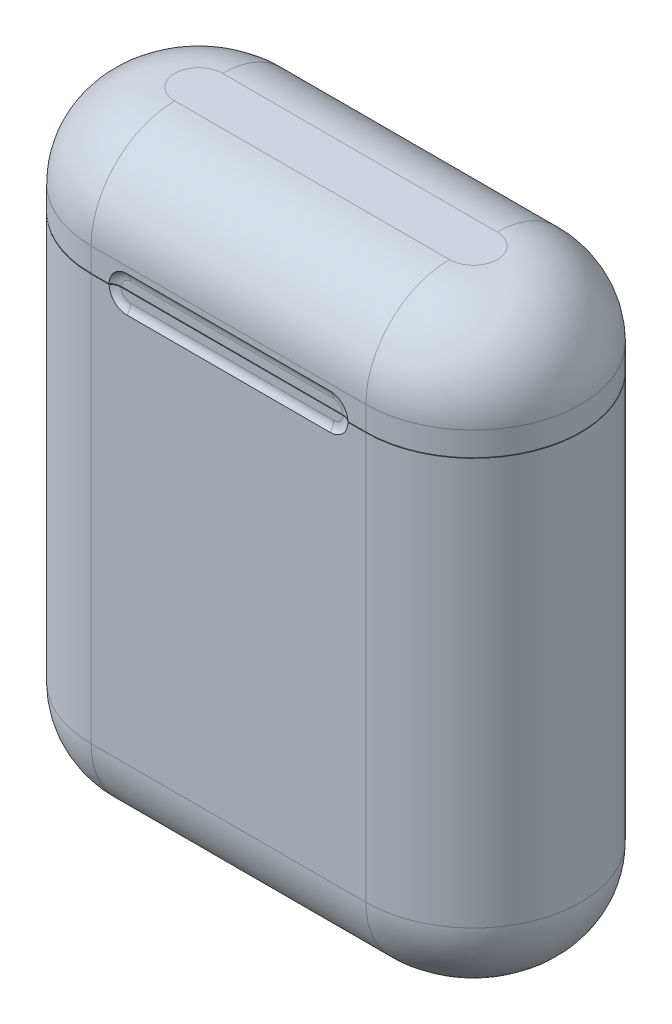
SolidWorks part; units mm, degrees
ref_plane "Front Plane" through (0, 0, 0) normal (0, 0, 1) x (1, 0, 0)
ref_plane "Top Plane" through (0, 0, 0) normal (0, 1, 0) x (1, 0, 0)
ref_plane "Right Plane" through (0, 0, 0) normal (1, 0, 0) x (0, 0, -1)
sketch "Sketch1" plane through (0, 0, 0) normal (0, 1, 0) x (1, 0, 0)
  line L0 (-29.21, 45.72) -> (29.21, 45.72)
  line L1 (29.21, 0) -> (-29.21, 0)
  arc A0 (29.21, 0) -> (29.21, 45.72) centre (29.21, 22.86) ccw
  arc A1 (-29.21, 45.72) -> (-29.21, 0) centre (-29.21, 22.86) ccw
  point P1 (0, 0)
  dimension "D1" = 22.86
  dimension "D2" = 58.42
extrude "Boss-Extrude1" add sketch "Sketch1" along normal blind 127 and the other way blind 0.254
fillet "Fillet1" radius 17.78 8 edges at (0, -0.254, 0) (-52.07, -0.254, -22.86) (0, -0.254, -45.72) (52.07, -0.254, -22.86) (52.07, 127, -22.86) (-52.07, 127, -22.86) (0, 127, -45.72) (0, 127, 0)
sketch "Sketch2" plane through (0, 0, 0) normal (0, 0, 1) x (1, 0, 0)
  line L0 (-21.59, 104.0797) -> (21.59, 104.0797) construction
  line L1 (-21.59, 107.8897) -> (21.59, 107.8897)
  line L2 (-21.59, 100.2697) -> (21.59, 100.2697)
  line L3 (29.21, 109.22) -> (-29.21, 109.22) construction
  arc A0 (-21.59, 107.8897) -> (-21.59, 100.2697) centre (-21.59, 104.0797) ccw
  arc A1 (21.59, 100.2697) -> (21.59, 107.8897) centre (21.59, 104.0797) ccw
  point P2 (0, 104.0797)
  point P9 (0, 109.22)
  point P10 (-25.4, 104.0797)
  dimension "D1" = 43.18
  dimension "D2" = 25.4
extrude "Cut-Extrude1" cut sketch "Sketch2" against normal blind 0.762
fillet "Fillet4" radius 2.54 4 edges at (0, 107.8897, -0.762) (-25.4, 104.0797, -0.762) (25.4, 104.0797, -0.762) (0, 100.2697, -0.762)
ref_plane "Plane1" through (0, 104.0797, 0) normal (0, 1, 0) x (1, 0, 0)
sketch "Sketch5" plane through (0, 104.0797, 0) normal (0, 1, 0) x (1, 0, 0)
  line L0 (29.21, 0) -> (-29.21, 0) construction
  line L1 (-29.21, 45.72) -> (29.21, 45.72) construction
  line L2 (29.21, 0) -> (-29.21, 0)
  line L3 (-29.21, 45.72) -> (29.21, 45.72)
  arc A0 (29.21, 0) -> (29.21, 45.72) centre (29.21, 22.86) ccw construction
  arc A1 (-29.21, 45.72) -> (-29.21, 0) centre (-29.21, 22.86) ccw construction
  arc A2 (29.21, 0) -> (29.21, 45.72) centre (29.21, 22.86) ccw
  arc A3 (-29.21, 45.72) -> (-29.21, 0) centre (-29.21, 22.86) ccw
ref_plane "Plane2" through (-25.4, 0, 0) normal (1, 0, 0) x (0, 0, -1)
sketch "Sketch6" plane through (-25.4, 0, 0) normal (1, 0, 0) x (0, 0, -1)
  line L0 (0, 109.22) -> (0, 17.526) construction
  line L1 (0.127, 104.1432) -> (0, 104.1432)
  line L2 (0.127, 104.1432) -> (0.127, 104.0162)
  line L3 (0.127, 104.0162) -> (0, 104.0162)
  line L4 (0, 104.1432) -> (0, 104.0162)
  line L5 (45.72, 104.0797) -> (0, 104.0797) construction
  dimension "D1" = 0.127
  dimension "D2" = 0.0635
  dimension "D3" = 0.127
sweep "Cut-Sweep1" cut profiles "Sketch6" path "Sketch5"
sketch "Sketch7" plane through (0, 0, 0) normal (0, 0, 1) x (1, 0, 0)
  line L0 (-25.1224, 104.0221) -> (25.2675, 103.9952)
  line L1 (25.2675, 103.9952) -> (25.2675, 104.1183)
  line L2 (25.2675, 104.1183) -> (-25.1952, 104.1758)
  line L3 (-25.1952, 104.1758) -> (-25.324, 104.147)
  line L4 (-25.324, 104.147) -> (-25.324, 104.0276)
  line L5 (-25.324, 104.0276) -> (-25.1224, 104.0221)
extrude "Cut-Extrude2" cut sketch "Sketch7" against normal blind 1.27
sketch "Sketch8" plane through (0, -0.254, 0) normal (0, -1, 0) x (1, 0, 0)
  line L0 (-8.89, -22.86) -> (6.35, -22.86) construction
  line L1 (-8.89, -20.32) -> (6.35, -20.32)
  line L2 (-8.89, -25.4) -> (6.35, -25.4)
  arc A0 (-8.89, -20.32) -> (-8.89, -25.4) centre (-8.89, -22.86) ccw
  arc A1 (6.35, -25.4) -> (6.35, -20.32) centre (6.35, -22.86) ccw
  arc A5 (29.21, -27.94) -> (29.21, -17.78) centre (29.21, -22.86) ccw construction
  arc A6 (-29.21, -17.78) -> (-29.21, -27.94) centre (-29.21, -22.86) ccw construction
  point P3 (-1.27, -22.86)
  dimension "D1" = 22.86
  dimension "D2" = 20.32
  dimension "D3" = 15.24
extrude "Cut-Extrude3" cut sketch "Sketch8" against normal blind 13.97
sketch "Sketch11" plane through (0, -0.254, 0) normal (0, -1, 0) x (1, 0, 0)
  line L0 (-8.89, -22.86) -> (6.35, -22.86) construction
  line L1 (-8.89, -19.6554) -> (6.35, -19.6554)
  line L2 (-8.89, -26.0646) -> (6.35, -26.0646)
  line L3 (-8.89, -22.86) -> (6.35, -22.86) construction
  line L4 (-8.89, -20.3428) -> (6.35, -20.3428)
  line L5 (-8.89, -25.3772) -> (6.35, -25.3772)
  arc A0 (-8.89, -19.6554) -> (-8.89, -26.0646) centre (-8.89, -22.86) ccw
  arc A1 (6.35, -26.0646) -> (6.35, -19.6554) centre (6.35, -22.86) ccw
  arc A2 (-8.89, -20.3428) -> (-8.89, -25.3772) centre (-8.89, -22.86) ccw
  arc A3 (6.35, -25.3772) -> (6.35, -20.3428) centre (6.35, -22.86) ccw
  point P4 (-1.27, -22.86)
  point P11 (-1.27, -22.86)
extrude "Cut-Extrude-Thin2" cut sketch "Sketch11" against normal blind 1.27 thin thin type one direction wall 0.127
sketch "Sketch12" plane through (0, 0, -45.72) normal (0, 0, -1) x (-1, 0, 0)
  circle A0 centre (0, 30.4737) radius 7.0684
extrude "Cut-Extrude-Thin3" cut sketch "Sketch12" against normal blind 1.27 thin thin type one direction wall 0.127
sketch "Sketch13" plane through (0, 0, -45.72) normal (0, 0, -1) x (-1, 0, 0)
  line L0 (-29.21, 104.0162) -> (29.21, 104.0162) construction
  line L1 (20.32, 101.4762) -> (20.32, 104.0162)
  line L2 (-29.21, 104.0162) -> (29.21, 104.0162) construction
  line L3 (17.78, 98.9362) -> (-17.78, 98.9362)
  line L4 (-20.32, 101.4762) -> (-20.32, 104.0162)
  line L5 (52.07, 17.526) -> (52.07, 104.0162) construction
  line L6 (-52.07, 104.0162) -> (-52.07, 17.526) construction
  arc A0 (-20.32, 101.4762) -> (-17.78, 98.9362) centre (-17.78, 101.4762) ccw
  arc A1 (17.78, 98.9362) -> (20.32, 101.4762) centre (17.78, 101.4762) ccw
  dimension "D1" = 34.29
  dimension "D2" = 34.29
  dimension "D3" = 5.08
extrude "Cut-Extrude-Thin4" cut sketch "Sketch13" against normal blind 1.27 and the other way through all thin thin type one direction wall 0.127
sketch "Sketch14" plane through (0, 0, -45.72) normal (0, 0, -1) x (-1, 0, 0)
  line L0 (-20.193, 104.0162) -> (20.193, 104.0162) construction
  line L1 (-15.367, 104.0162) -> (-15.3416, 104.0162)
  line L2 (-15.367, 104.0162) -> (-15.367, 99.0632)
  line L3 (-15.367, 99.0632) -> (-15.3416, 99.0632)
  line L4 (-15.3416, 104.0162) -> (-15.3416, 99.0632)
  line L5 (-17.78, 99.0632) -> (17.78, 99.0632) construction
  line L6 (-20.193, 104.0162) -> (20.193, 104.0162) construction
  line L7 (15.367, 104.0162) -> (15.3416, 104.0162)
  line L8 (15.367, 104.0162) -> (15.367, 99.0632)
  line L9 (15.367, 99.0632) -> (15.3416, 99.0632)
  line L10 (15.3416, 104.0162) -> (15.3416, 99.0632)
  line L11 (20.193, 104.0162) -> (20.193, 101.4762) construction
  line L12 (-20.193, 101.4762) -> (-20.193, 104.0162) construction
  dimension "D1" = 0.0254
  dimension "D2" = 0.0254
  dimension "D3" = 4.826
  dimension "D4" = 4.826
extrude "Cut-Extrude-Thin5" cut sketch "Sketch14" against normal blind 1.27 thin thin type one direction wall 0.0254
